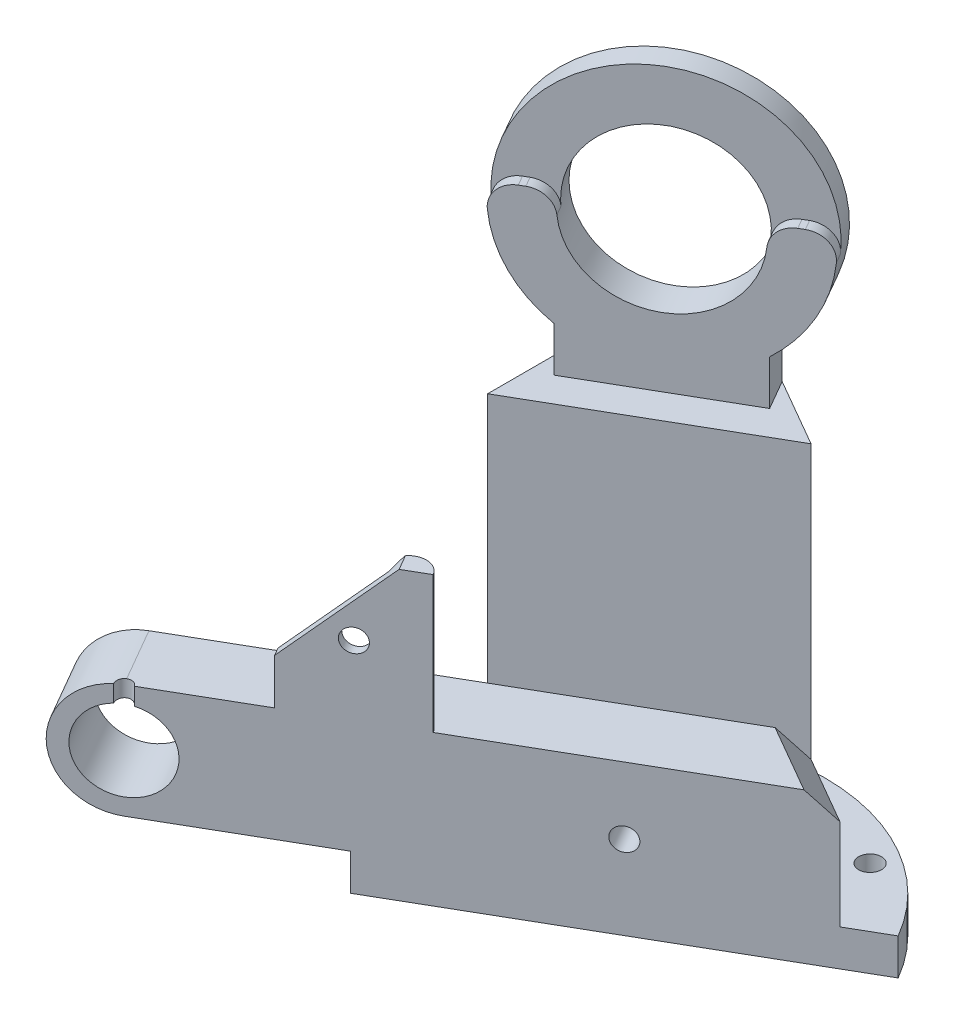
SolidWorks part; units mm, degrees
ref_plane "Front Plane" through (0, 0, 0) normal (0, 0, 1) x (1, 0, 0)
ref_plane "Top Plane" through (0, 0, 0) normal (0, 1, 0) x (1, 0, 0)
ref_plane "Right Plane" through (0, 0, 0) normal (1, 0, 0) x (0, 0, -1)
sketch "Sketch4" plane through (0, 0, 0) normal (0, 1, 0) x (1, 0, 0)
  circle A1 centre (0, 0) radius 55.88
  dimension "D2" = 111.76
extrude "Boss-Extrude2" add sketch "Sketch4" along normal blind 10.16
sketch "Sketch8" plane through (0, 10.16, 0) normal (0, 1, 0) x (1, 0, 0)
  line L1 (0, 43.9941) -> (-38.1, 21.997)
  line L2 (-38.1, 21.997) -> (-38.1, -21.997)
  line L3 (-38.1, -21.997) -> (0, -43.9941)
  line L4 (0, -43.9941) -> (38.1, -21.997)
  line L5 (38.1, -21.997) -> (38.1, 21.997)
  line L6 (38.1, 21.997) -> (0, 43.9941)
  circle A0 centre (0, 0) radius 38.1 construction
  dimension "D1" = 76.2
extrude "Boss-Extrude4" add sketch "Sketch8" along normal blind 101.6
sketch "Sketch9" plane through (-19.05, 0, -32.9956) normal (-0.5, 0, -0.866) x (-0.866, 0, 0.5)
  line L1 (21.997, 111.76) -> (-21.997, 111.76)
  line L2 (21.997, 111.76) -> (21.997, 124.226)
  line L4 (-21.997, 111.76) -> (-21.997, 124.226)
  arc A2 (21.997, 124.226) -> (-21.997, 124.226) centre (0, 152.4) ccw
extrude "Boss-Extrude5" add sketch "Sketch9" against normal blind 9.525
sketch "Sketch10" plane through (19.05, 0, 32.9956) normal (0.5, 0, 0.866) x (0.866, 0, -0.5)
  line L3 (-21.997, 111.76) -> (21.997, 111.76)
  line L4 (21.997, 111.76) -> (21.997, 124.226)
  line L5 (-21.997, 124.226) -> (-21.997, 111.76)
  line L6 (-21.997, 111.76) -> (21.997, 111.76)
  line L7 (21.997, 111.76) -> (21.997, 124.226)
  line L8 (-21.997, 124.226) -> (-21.997, 111.76)
  arc A1 (21.997, 124.226) -> (-21.997, 124.226) centre (0, 152.4) ccw
  arc A4 (21.997, 124.226) -> (-21.997, 124.226) centre (0, 152.4) ccw
  dimension "D1" = 0
extrude "Boss-Extrude6" add sketch "Sketch10" against normal blind 9.525
sketch "Sketch12" plane through (-19.05, 0, -32.9956) normal (-0.5, 0, -0.866) x (-0.866, 0, 0.5)
  circle A0 centre (0, 152.4) radius 21.5
  point P3 (0, 152.4)
  dimension "D1" = 43
extrude "Cut-Extrude4" cut sketch "Sketch12" against normal up to surface (76.2 mm away) up to face at (19.05, 92.7017, 32.9956)
sketch "Sketch13" plane through (-19.05, 0, 10.9985) normal (-0.866, 0, 0.5) x (0.5, 0, 0.866)
  line L0 (0, 111.76) -> (0, 10.16) construction
  line L1 (-19.05, 41.91) -> (19.05, 41.91)
  line L2 (-19.05, 41.91) -> (-19.05, 111.76)
  line L3 (-19.05, 111.76) -> (19.05, 111.76)
  line L4 (19.05, 41.91) -> (19.05, 111.76)
  line L5 (-19.05, 41.91) -> (19.05, 111.76) construction
  line L6 (-19.05, 111.76) -> (19.05, 41.91) construction
  line L7 (-38.1, 111.76) -> (0, 111.76) construction
  point P0 (0, 76.835)
  dimension "D1" = 69.85
  dimension "D2" = 0
  dimension "D3" = 38.1
extrude "Cut-Extrude5" cut sketch "Sketch13" against normal mid plane 152.4
sketch "Sketch14" plane through (-19.05, 0, -32.9956) normal (-0.5, 0, -0.866) x (-0.866, 0, 0.5)
  circle A0 centre (0, 124.7701) radius 3.8666
ref_plane "Plane1" through (0, 0, 0) normal (-0.5, 0, -0.866) x (-0.866, 0, 0.5)
sketch "Sketch17" plane through (0, 0, 0) normal (-0.5, 0, -0.866) x (-0.866, 0, 0.5)
  circle A0 centre (0, 152.4) radius 162.4584
  dimension "D1" = 324.9168
ref_plane "Plane3" through (38.1, 41.91, -21.997) normal (0, -1, 0) x (-1, 0, 0)
sketch "Sketch22" plane through (0, 0, 0) normal (-0.5, 0, -0.866) x (-0.866, 0, 0.5)
  line L5 (43.9941, 41.91) -> (102.101, 41.91)
  line L6 (102.101, 10.16) -> (43.9941, 10.16)
  line L8 (43.9941, 10.16) -> (21.997, 10.16)
  line L9 (21.997, 10.16) -> (21.997, 41.91)
  line L10 (21.997, 111.76) -> (21.997, 10.16) construction
  line L11 (21.997, 41.91) -> (43.9941, 41.91)
  arc A2 (102.101, 10.16) -> (102.101, 41.91) centre (102.101, 26.035) ccw
  circle A3 centre (0, 152.4) radius 162.4584 construction
  dimension "D1" = 31.75
ref_plane "Plane4" through (23.876, 0, 41.3544) normal (0.5, 0, 0.866) x (0.866, 0, -0.5)
extrude "Boss-Extrude10" add sketch "Sketch22" along normal mid plane 38.1
sketch "Sketch28" plane through (9.525, 0, 16.4978) normal (0.5, 0, 0.866) x (0.866, 0, -0.5)
  circle A0 centre (-102.101, 26.035) radius 11.2395
  dimension "D1" = 22.479
extrude "Cut-Extrude9" cut sketch "Sketch28" against normal up to surface (38.1 mm away) up to face at (-68.1724, 22.86, 17.3623)
sketch "Sketch29" plane through (9.525, 0, 16.4978) normal (0.5, 0, 0.866) x (0.866, 0, -0.5)
  line L1 (-104.4849, 17.907) -> (-122.1961, 17.907)
  line L2 (-104.4849, 17.907) -> (-104.4849, 34.163)
  line L3 (-104.4849, 34.163) -> (-122.1961, 34.163)
  line L4 (-122.1961, 17.907) -> (-122.1961, 34.163)
  line L5 (-104.4849, 17.907) -> (-122.1961, 34.163) construction
  line L6 (-104.4849, 34.163) -> (-122.1961, 17.907) construction
  circle A0 centre (-102.101, 26.035) radius 11.2395 construction
  arc A1 (-102.101, 41.91) -> (-102.101, 10.16) centre (-102.101, 26.035) ccw construction
  circle A2 centre (-102.101, 26.035) radius 11.2395
  circle A3 centre (-102.101, 26.035) radius 11.2395
  arc A4 (-102.101, 41.91) -> (-102.101, 10.16) centre (-102.101, 26.035) ccw
  point P0 (-113.3405, 26.035)
  circle M3 centre (-102.101, 26.035) radius 11.2395
  arc M7 (-102.101, 41.91) -> (-102.101, 10.16) centre (-102.101, 26.035) ccw
  dimension "D1" = 16.256
  dimension "D2" = 0
extrude "Cut-Extrude10" cut sketch "Sketch29" against normal blind 7.366 contours L3 L1 M3 M7 region at (-89.8086, 26.035, 73.8481)
chamfer "Chamfer1" distance 6.35 angle 45 2 edges at (38.1, 41.91, -10.9985) (28.575, 41.91, -27.4963)
sketch "Sketch30" plane through (0, 41.91, 0) normal (0, 1, 0) x (1, 0, 0)
  line L0 (-97.9471, -34.5527) -> (-78.8971, -67.5483) construction
  circle A0 centre (-88.4221, -51.0505) radius 2.1
  dimension "D1" = 4.2
extrude "Cut-Extrude11" cut sketch "Sketch30" against normal blind 7.366
sketch "Sketch31" plane through (0, 10.16, 0) normal (0, 1, 0) x (1, 0, 0)
  circle A0 centre (0, 0) radius 49.53 construction
  circle A4 centre (-49.089, 6.5948) radius 3.175
  circle A5 centre (26.9253, 41.5722) radius 3.175
  dimension "D1" = 6.35
  dimension "D2" = 99.06
  dimension "D3" = 6.35
extrude "Cut-Extrude12" cut sketch "Sketch31" against normal through all
mirror "Mirror1" about plane through (0, 0, 0) normal (-0.5, 0, -0.866) of "Cut-Extrude12"
sketch "Sketch33" plane through (0, 41.91, 0) normal (0, 1, 0) x (1, 0, 0)
  line L0 (140.6931, 81.2292) -> (-140.6931, -81.2292) construction
  line L5 (-43.4119, -22.0798) -> (-63.0924, -33.4424)
  line L6 (-63.0924, -33.4424) -> (-61.8003, -35.6804)
  line L7 (-61.8003, -35.6804) -> (-60.5427, -37.8586)
  line L8 (-60.5427, -37.8586) -> (-40.9154, -26.5041)
  arc A0 (-40.9154, -26.5041) -> (-43.4119, -22.0798) centre (-38.2434, -22.0798) ccw
extrude "Boss-Extrude11" add sketch "Sketch33" along normal blind 38.1
chamfer "Chamfer2" distance 25.4 angle 45 1 edges at (-61.8176, 80.01, 35.6505)
sketch "Sketch34" plane through (-1.2921, 0, -2.238) normal (-0.5, 0, -0.866) x (-0.866, 0, 0.5)
  circle A0 centre (55.1848, 61.1591) radius 3.175
  dimension "D1" = 6.35
extrude "Cut-Extrude13" cut sketch "Sketch34" against normal up to surface (5.0994 mm away) up to face at (-50.7291, 53.9288, 32.1813)
sketch "Sketch35" plane through (19.05, 0, 32.9956) normal (0.5, 0, 0.866) x (0.866, 0, -0.5)
  circle A0 centre (0, 23.2801) radius 3.175
  dimension "D1" = 6.35
extrude "Cut-Extrude14" cut sketch "Sketch35" against normal through all
sketch "Sketch36" plane through (-19.05, 0, 10.9985) normal (-0.866, 0, 0.5) x (0.5, 0, 0.866)
  line L0 (0, 0) -> (0, 199.814) construction
  line L1 (-31.75, 193.0158) -> (31.75, 193.0158)
  line L2 (-31.75, 193.0158) -> (-31.75, 156.3059)
  line L3 (-31.75, 156.3059) -> (31.75, 156.3059)
  line L4 (31.75, 193.0158) -> (31.75, 156.3059)
  line L5 (-55.88, 0) -> (55.88, 0) construction
  line L6 (0, 17.4625) -> (0, -17.4625) construction
  point P10 (0, 156.3059)
  dimension "D1" = 63.5
extrude "Cut-Extrude15" cut sketch "Sketch36" against normal mid plane 127
fillet "Fillet1" radius 6.35 6 edges at (-33.391, 156.3059, -15.5504) (3.2285, 156.3059, -36.6926) (15.6887, 156.3059, -43.8865) (45.8512, 156.3059, 8.3564) (-15.6887, 156.3059, 43.8865) (-45.8512, 156.3059, -8.3564)
sketch "Sketch37" plane through (0, 0, 0) normal (-0.5, 0, -0.866) x (-0.866, 0, 0.5)
  line L1 (-74.8839, -3.3145) -> (135.8585, -3.3145)
  line L2 (-74.8839, -3.3145) -> (-74.8839, 197.9105)
  line L3 (-74.8839, 197.9105) -> (135.8585, 197.9105)
  line L4 (135.8585, -3.3145) -> (135.8585, 197.9105)
extrude "Cut-Extrude16" cut sketch "Sketch37" against normal through all
